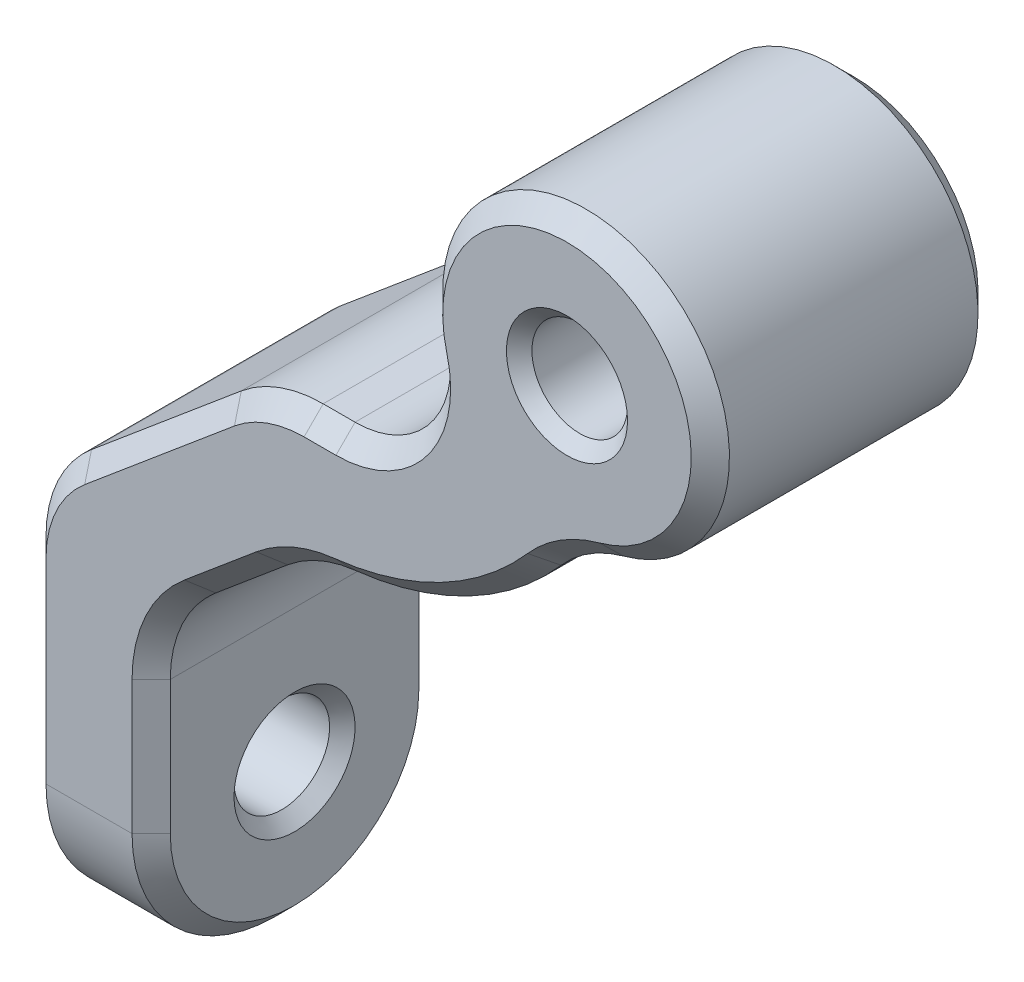
SolidWorks part; units mm, degrees
material "POM Acetal Copolymer"
ref_plane "Front" through (0, 0, 0) normal (0, 0, 1) x (1, 0, 0)
ref_plane "Top" through (0, 0, 0) normal (0, 1, 0) x (1, 0, 0)
ref_plane "Right" through (0, 0, 0) normal (1, 0, 0) x (0, 0, -1)
sketch "Sketch1" plane through (0, 0, 0) normal (0, 0, 1) x (1, 0, 0)
  line L1 (-13.05, 0) -> (-13.05, 8.6917)
  line L2 (-13.05, 0) -> (-16.95, 0)
  line L6 (-16.95, 10.6391) -> (-16.95, 0)
  line L7 (-15.5212, 13.7033) -> (-10.8217, 17.6466)
  line L8 (-8.2506, 18.5824) -> (-7.2507, 18.5824)
  line L9 (-9.3658, 13.6483) -> (-11.6212, 11.7559)
  line L11 (0, 23.5) -> (0, 0) construction
  line L13 (-13.05, 0) -> (0, 0) construction
  arc A0 (-16.95, 10.6391) -> (-15.5212, 13.7033) centre (-12.95, 10.6391) cw
  arc A1 (-10.8217, 17.6466) -> (-8.2506, 18.5824) centre (-8.2506, 14.5824) cw
  arc A2 (-7.2507, 18.5824) -> (-4.3504, 22.3495) centre (-7.2507, 21.5824) ccw
  arc A3 (-4.3504, 22.3495) -> (1.1813, 19.1578) centre (0, 23.5) cw
  arc A4 (1.1813, 19.1578) -> (-0.783, 17.9275) centre (2.2313, 15.2981) ccw
  arc A5 (-0.783, 17.9275) -> (-7.2301, 14.5604) centre (-8.3189, 24.5009) cw
  arc A6 (-7.2301, 14.5604) -> (-9.3658, 13.6483) centre (-6.7946, 10.5842) ccw
  arc A7 (-11.6212, 11.7559) -> (-13.05, 8.6917) centre (-9.05, 8.6917) ccw
  circle A8 centre (0, 23.5) radius 1.5
  dimension "D3" = 3
  dimension "D4" = 4.5
  dimension "D9" = 4
  dimension "D11" = 50
  dimension "D12" = 18.5824
  dimension "D13" = 3
  dimension "D14" = 10
  dimension "D15" = 2.2313
  dimension "D5" = 23.5
  dimension "D6" = 13.05
  dimension "D7" = 3.9
  dimension "D8" = 8.6917
  dimension "D10" = 10.6391
  dimension "D16" = 6.7946
extrude "Boss-Extrude1" add sketch "Sketch1" along normal mid plane 9 separate body
fillet "Fillet1" 2 edges at (-15, 0, -4.5) (-15, 0, 4.5) type full round first side face at (-9.2755, 13.8154, -4.5) second side face at (-9.2755, 13.8154, 4.5) middle face at (-15, 0, 0)
sketch "Sketch3" plane through (-16.95, 0, 0) normal (-1, 0, 0) x (0, 0, 1)
  circle A0 centre (0, 4.5) radius 1.5
  dimension "D1" = 3
extrude "Cut-Extrude1" cut sketch "Sketch3" against normal up to next
chamfer "Chamfer1" distance 0.6 angle 45 28 edges at (-13.05, 0, 0) (-13.05, 6.5958, -4.5) (-13.05, 6.5958, 4.5) (-12.6752, 10.3822, -4.5) (-12.6752, 10.3822, 4.5) (-10.4935, 12.7021, -4.5) (-10.4935, 12.7021, 4.5) (-8.3656, 14.2628, -4.5) (-8.3656, 14.2628, 4.5) (-3.6896, 15.637, -4.5) (-3.6896, 15.637, 4.5) (0.1081, 18.688, -4.5) (0.1081, 18.688, 4.5) (2.2489, 27.3978, -4.5) (2.2489, 27.3978, 4.5) (-4.8736, 19.7523, -4.5) (-4.8736, 19.7523, 4.5) (-7.7506, 18.5824, -4.5) (-7.7506, 18.5824, 4.5) (-9.6186, 18.3412, -4.5) (-9.6186, 18.3412, 4.5) (-13.1714, 15.675, -4.5) (-13.1714, 15.675, 4.5) (-16.5752, 12.3296, -4.5) (-16.5752, 12.3296, 4.5) (-16.95, 7.5696, -4.5) (-16.95, 7.5696, 4.5) (-16.95, 0, 0)
chamfer "Chamfer2" distance 0.4 angle 45 4 edges at (-13.05, 4.5, 1.5) (-16.95, 4.5, 1.5) (1.5, 23.5, -4.5) (1.5, 23.5, 4.5)
